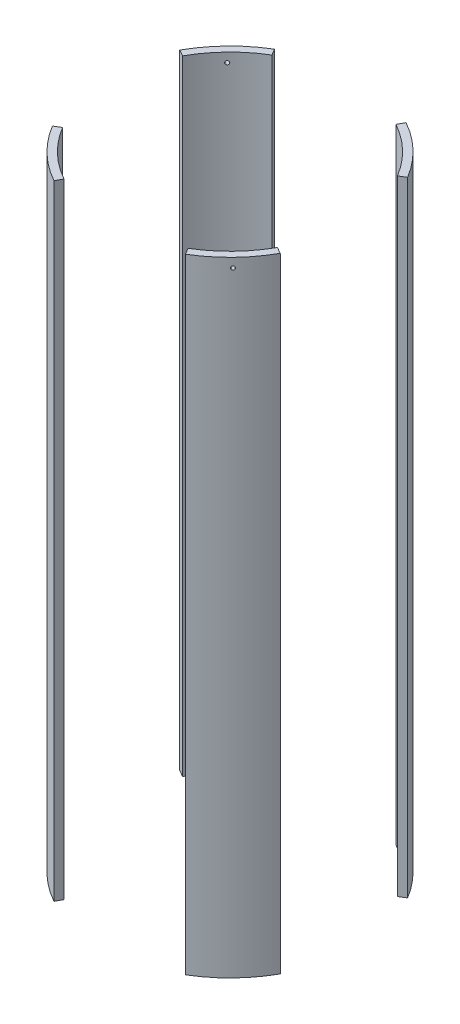
SolidWorks part; units mm, degrees
material "6061-T6 (SS)"
ref_plane "Front Plane" through (0, 0, 0) normal (0, 0, 1) x (1, 0, 0)
ref_plane "Top Plane" through (0, 0, 0) normal (0, 1, 0) x (1, 0, 0)
ref_plane "Right Plane" through (0, 0, 0) normal (1, 0, 0) x (0, 0, -1)
sketch "Sketch2" plane through (0, 0, 0) normal (0, 1, 0) x (1, 0, 0)
  circle A0 centre (0, 0) radius 88.9
  circle A1 centre (0, 0) radius 83.82
  dimension "D1" = 177.8
  dimension "D2" = 167.64
extrude "Boss-Extrude1" add sketch "Sketch2" along normal mid plane 428.625
sketch "Sketch3" plane through (0, 0, 0) normal (0, 1, 0) x (1, 0, 0)
  line L0 (0, 0) -> (169.6618, 101.6776)
  line L1 (-58.1167, 96.9749) -> (0, 0)
  line L2 (0, 0) -> (53.9, 96.9749)
  line L3 (53.9, 96.9749) -> (-58.1167, 96.9749)
  line L4 (0, 0) -> (70.9917, -118.4586)
  line L5 (70.9917, -118.4586) -> (-65.8409, -118.4586)
  line L6 (-65.8409, -118.4586) -> (0, 0)
  line L7 (169.6618, 101.6776) -> (169.6618, -94.3004)
  line L8 (169.6618, -94.3004) -> (0, 0)
  line L9 (0, 0) -> (-123.7413, 68.7771)
  line L10 (-123.7413, 68.7771) -> (-123.7413, -74.1577)
  line L11 (-123.7413, -74.1577) -> (0, 0)
  dimension "D1" = 60
  dimension "D2" = 60
  dimension "D3" = 60
  dimension "D4" = 60
  dimension "D5" = 30
  dimension "D6" = 30
extrude "Cut-Extrude1" cut sketch "Sketch3" against normal through all both and the other way through all contours L8 L7 L0 | L2 L3 L1 | L10 L11 L9 | L6 L5 L4 region at (-1.4056, 0, -64.65) region at (1.7169, 0, 78.9724) region at (113.1078, 0, -2.4591) region at (-82.4942, 0, 1.7935)
ref_plane "Bolt reference plane" through (-56.3092, 0, 58.1758) normal (0.6955, 0, -0.7185) x (-0.7185, 0, -0.6955)
sketch "Sketch5" plane through (-56.3092, 0, 58.1758) normal (0.6955, 0, -0.7185) x (-0.7185, 0, -0.6955)
  circle A0 centre (-0.0228, 207.9625) radius 1.27
  dimension "D1" = 2.54
  dimension "D2" = 21.717
  dimension "D3" = 6.35
extrude "Top bolt holes" cut sketch "Sketch5" against normal through all
sketch "Sketch6" plane through (0, -214.3125, 0) normal (0, -1, 0) x (-1, 0, 0)
  line L0 (71.8974, -43.0878) -> (40.7211, -73.2638) construction
  line L1 (0, 0) -> (61.8287, -63.8782) construction
  circle A0 centre (60.0621, -62.0531) radius 1.27
  arc A1 (43.189, -77.7041) -> (76.2548, -45.6992) centre (0, 0) ccw construction
  dimension "D2" = 2.54
  dimension "D1" = 86.36
extrude "Bottom bolt holes" cut sketch "Sketch6" against normal blind 31.75
pattern_circular "Bolt pattern" count 4 over 360 about axis through (0, 214.3125, 0) along (0, 1, 0) of "Top bolt holes", "Bottom bolt holes"
equation "\"D1@Boss-Extrude1\"=3*12"
